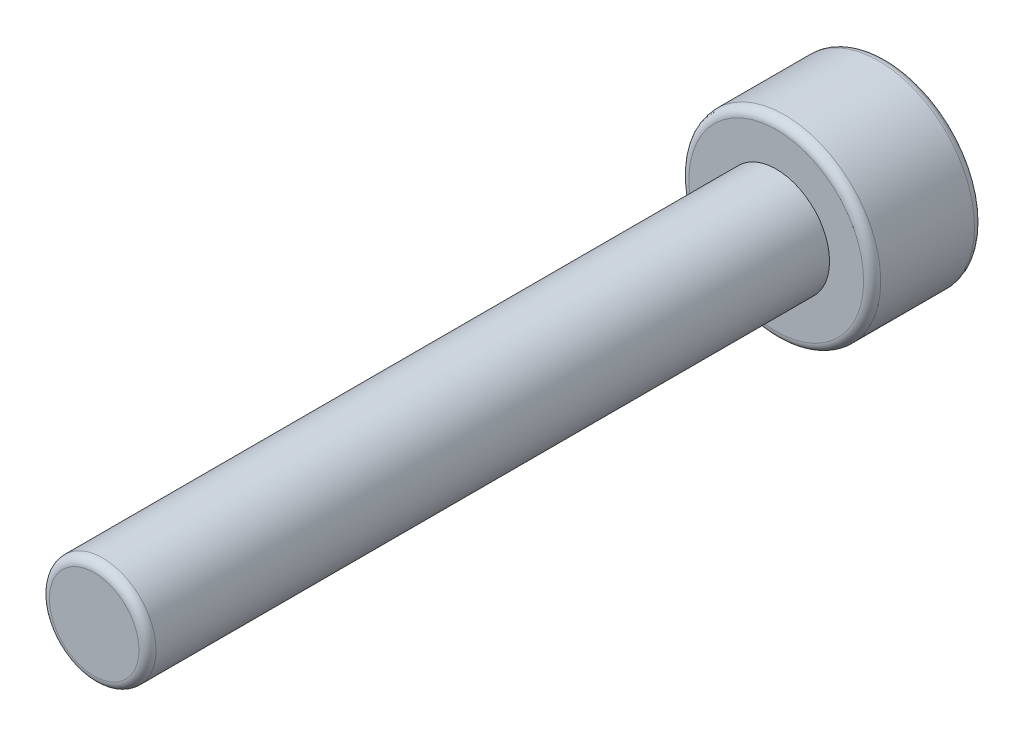
SolidWorks part; units mm, degrees
ref_plane "Front Plane" through (0, 0, 0) normal (0, 0, 1) x (1, 0, 0)
ref_plane "Top Plane" through (0, 0, 0) normal (0, 1, 0) x (1, 0, 0)
ref_plane "Right Plane" through (0, 0, 0) normal (1, 0, 0) x (0, 0, -1)
sketch "Sketch1" plane through (0, 0, 0) normal (0, 0, 1) x (1, 0, 0)
  circle A0 centre (0, 0) radius 1.25
  circle A1 centre (0, 0) radius 2.25
  dimension "D1" = 2.5
  dimension "D2" = 4.5
extrude "Boss-Extrude1" add sketch "Sketch1" along normal blind 16 contours A0 region at (0, 0, 0)
extrude "Boss-Extrude2" add sketch "Sketch1<3>" against normal blind 2.6 contours A0 | A1 A0 region at (0, 0, 0) region at (-2.1864, 0, 0)
sketch "Sketch1<3>" plane through (0, 0, 0) normal (0, 0, 1) x (1, 0, 0) same geometry as "Sketch1"
sketch "Sketch2" plane through (0, 0, -2.6) normal (0, 0, -1) x (-1, 0, 0)
  line L1 (0, 1.1547) -> (-1, 0.5774)
  line L2 (-1, 0.5774) -> (-1, -0.5774)
  line L3 (-1, -0.5774) -> (0, -1.1547)
  line L4 (0, -1.1547) -> (1, -0.5774)
  line L5 (1, -0.5774) -> (1, 0.5774)
  line L6 (1, 0.5774) -> (0, 1.1547)
  circle A0 centre (0, 0) radius 1 construction
  point P1 (0, 0)
  dimension "D1" = 2
extrude "Cut-Extrude1" cut sketch "Sketch2" against normal blind 1.4
fillet "Fillet1" radius 0.2 3 edges at (1.25, 0, 16) (2.25, 0, 0) (2.25, 0, -2.6)
